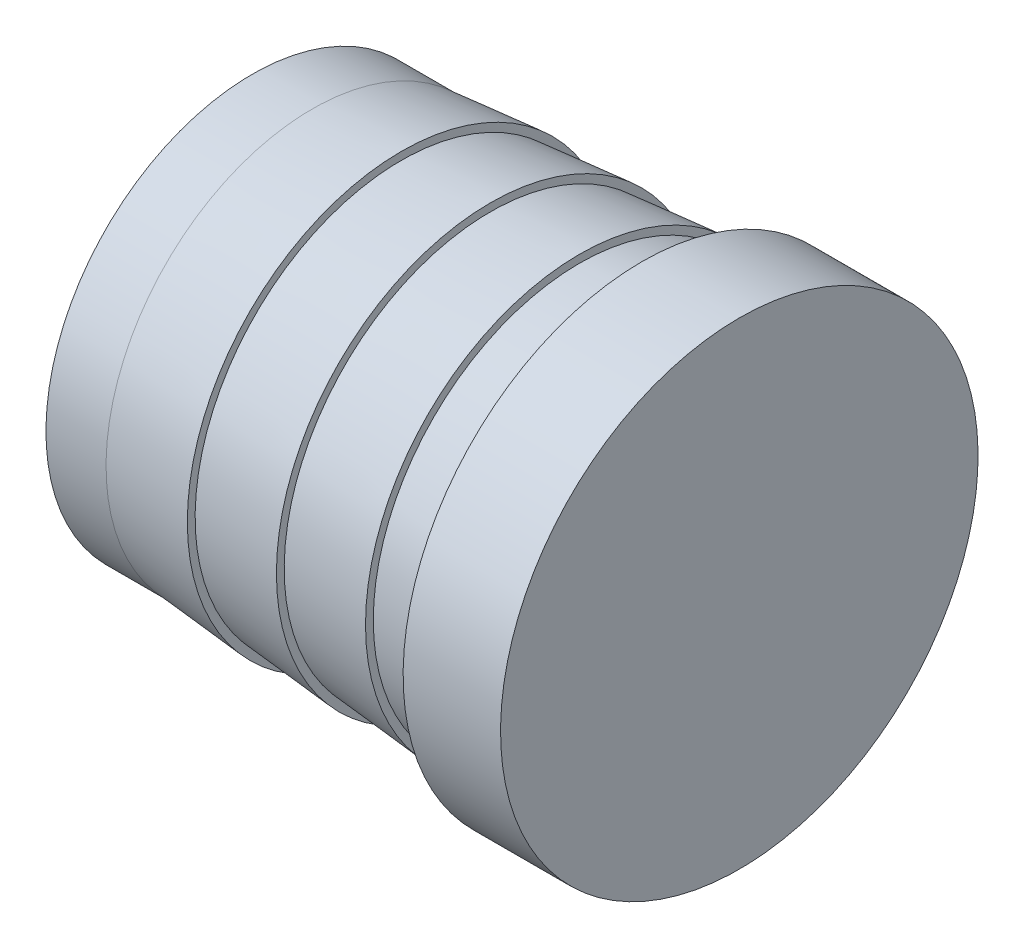
SolidWorks part; units mm, degrees
ref_plane "Front Plane" through (0, 0, 0) normal (0, 0, 1) x (1, 0, 0)
ref_plane "Top Plane" through (0, 0, 0) normal (0, 1, 0) x (1, 0, 0)
ref_plane "Right Plane" through (0, 0, 0) normal (1, 0, 0) x (0, 0, -1)
sketch "Sketch0" plane through (0, 0, 0) normal (0, 0, 1) x (1, 0, 0)
  line L0 (-9.525, 0) -> (-47.625, 0) construction
  line L1 (-47.625, 14.2875) -> (-47.625, -14.2875) construction
  line L2 (-9.525, 20.9232) -> (-9.525, -20.9232) construction
  line L3 (-9.525, 20.1612) -> (-9.525, -20.1612) construction
  line L4 (-9.525, 0) -> (0, 0) construction
  line L20 (0, 0) -> (0, 9.525) construction
  circle A0 centre (0, 0) radius 23.3426 construction
  point P19 (0, 23.3426)
  dimension "Pipe OD" = 46.6852
  dimension "P" = 38.1
  dimension "D" = 28.575
  dimension "Z" = 41.8465
  dimension "V" = 0.762
  dimension "H" = 47.625
  dimension "G" = 9.525
  dimension "L" = 47.625
sketch "Sketch1" plane through (0, 0, 0) normal (0, 0, 1) x (1, 0, 0)
  line L0 (-47.625, 14.2875) -> (-9.525, 14.2875)
  line L1 (-9.525, 20.9232) -> (-9.525, -20.9232) construction
  line L2 (-9.525, 14.2875) -> (-9.525, 20.1612)
  line L3 (-41.7513, 20.1612) -> (-47.625, 20.1612)
  line L4 (-47.625, 20.1612) -> (-47.625, 14.2875)
  line L5 (-41.7513, 20.1612) -> (-33.0416, 20.9232)
  line L6 (-33.0416, 20.9232) -> (-6.9125, 20.9232) construction
  line L7 (-9.525, 20.1612) -> (-6.9125, 20.1612)
  line L8 (-41.7513, 20.1612) -> (-6.9125, 20.1612) construction
  line L9 (-33.0416, 20.9232) -> (-33.0416, 20.1612)
  line L10 (-33.0416, 20.1612) -> (-24.3319, 20.9232)
  line L11 (-24.3319, 20.9232) -> (-24.3319, 20.1612)
  line L12 (-24.3319, 20.1612) -> (-15.6222, 20.9232)
  line L13 (-15.6222, 20.9232) -> (-15.6222, 20.1612)
  line L14 (-15.6222, 20.1612) -> (-6.9125, 20.9232)
  line L15 (-6.9125, 20.9232) -> (-6.9125, 20.1612)
  line L16 (-6.9125, 20.9232) -> (-9.525, 20.9232) construction
  line L17 (-47.625, 0) -> (-9.525, 0) construction
  line L18 (-47.625, 20.9232) -> (-47.625, -20.9232) construction
  dimension "D1" = 5
revolve "Revolve1" add sketch "Sketch1" angle 360 about L17
sketch "Sketch2" plane through (-9.525, 0, 0) normal (1, 0, 0) x (0, 0, -1)
  circle A2 centre (0, 0) radius 23.3426
extrude "Boss-Extrude1" add sketch "Sketch2" along normal up to vertex (9.525 mm away) up to point (0, 0, 0)
other "CPoint1" parameters "Diameter"=38.1, "StubLength"=23.8125
ref_axis "Axis1" through (-19.525, 0, 0) along (1, 0, 0)
other "RPoint1"
